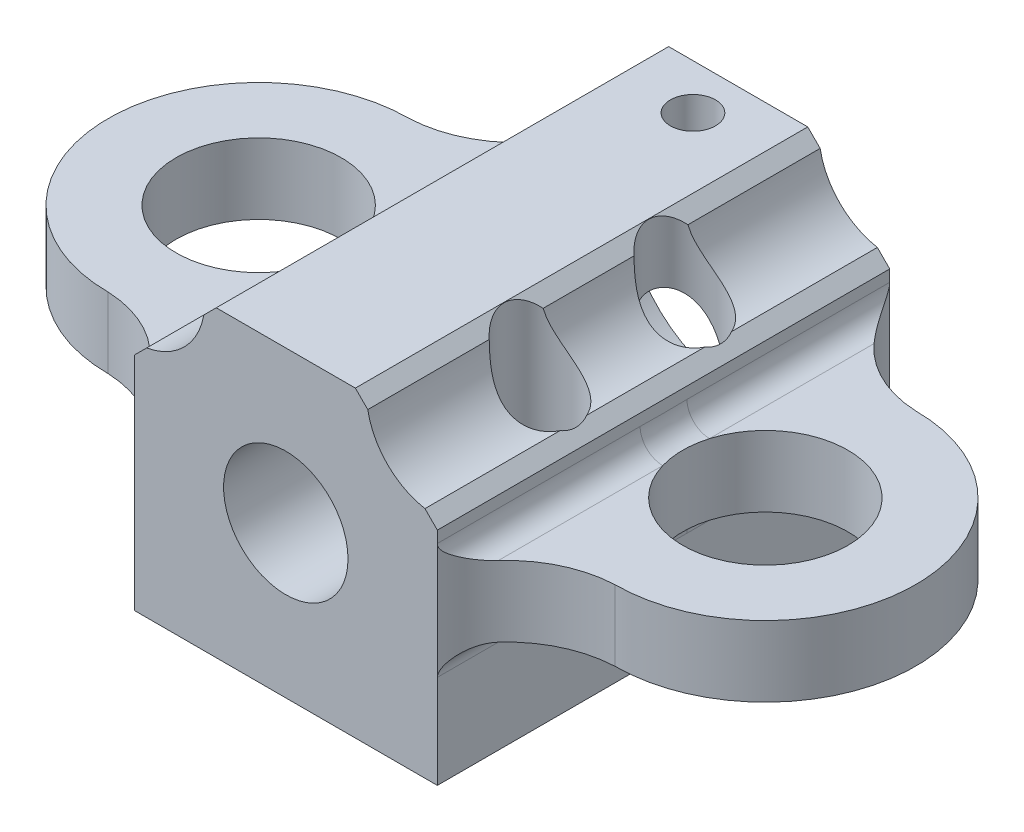
SolidWorks part; units mm, degrees
ref_plane "Front Plane" through (0, 0, 0) normal (0, 0, 1) x (1, 0, 0)
ref_plane "Top Plane" through (0, 0, 0) normal (0, 1, 0) x (1, 0, 0)
ref_plane "Right Plane" through (0, 0, 0) normal (1, 0, 0) x (0, 0, -1)
sketch "Sketch1" plane through (0, 0, 0) normal (0, 0, 1) x (1, 0, 0)
  line L0 (0, 0) -> (0, 69.4209) construction
  line L1 (8.509, 17.018) -> (-8.509, 17.018)
  line L2 (-8.509, 17.018) -> (-8.509, 0)
  line L3 (-8.509, 0) -> (8.509, 0)
  line L4 (8.509, 17.018) -> (8.509, 0)
  point P8 (0, 17.018)
  dimension "D1" = 17.018
  dimension "D2" = 17.018
extrude "Boss-Extrude1" add sketch "Sketch1" along normal blind 25.4
ref_plane "Plane1" through (0, 8.509, 0) normal (0, 1, 0) x (1, 0, 0)
sketch "Sketch2" plane through (0, 0, 0) normal (1, 0, 0) x (0, 0, -1)
  line L0 (-25.4, 8.509) -> (1.0345, 8.509) construction
  line L1 (-25.4, 0) -> (-25.4, 17.018) construction
  line L2 (-12.7, 14.859) -> (0, 14.859)
  line L3 (-12.7, 14.859) -> (-12.7, 12.0015)
  line L4 (-12.7, 12.0015) -> (-25.4, 12.0015)
  line L5 (-25.4, 12.0015) -> (-25.4, 8.509)
  line L6 (-25.4, 17.018) -> (0, 17.018) construction
  line L7 (-25.4, 8.509) -> (-12.1828, 8.509)
  line L9 (0, 0) -> (0, 17.018) construction
  line L10 (-12.1828, 8.509) -> (0, 8.509)
  line L11 (0, 8.509) -> (0, 14.859)
  dimension "D1" = 2.159
  dimension "D2" = 6.985
  dimension "D3" = 12.7
revolve "Cut-Revolve1" cut sketch "Sketch2" angle 360 about L7
sketch "Sketch4" plane through (0, 0, 0) normal (0, -1, 0) x (1, 0, 0)
  line L1 (-6, 17.0663) -> (6, 17.0663) construction
  line L2 (-6, 17.0663) -> (-6, 9.0663) construction
  line L3 (-6, 9.0663) -> (6, 9.0663) construction
  line L4 (6, 17.0663) -> (6, 9.0663) construction
  line L5 (-6, 17.0663) -> (6, 9.0663) construction
  line L6 (-6, 9.0663) -> (6, 17.0663) construction
  line L15 (-8.509, 25.4) -> (8.509, 25.4) construction
  circle A0 centre (-6, 17.0663) radius 1.016
  circle A1 centre (5.938, 17.0663) radius 1.016
  circle A2 centre (5.938, 8.9383) radius 1.016
  circle A3 centre (-6, 8.9383) radius 1.016
  point P0 (0, 13.0663)
  dimension "D3" = 2.032
  dimension "D1" = 12
  dimension "D2" = 8
  dimension "D6" = 8.3337
  dimension "D4" = 2
  dimension "D5" = 2
extrude "Cut-Extrude2" cut sketch "Sketch4" against normal through all
sketch "Sketch5" plane through (0, 8.509, 0) normal (0, 1, 0) x (1, 0, 0)
  line L1 (-14.1338, -12.7) -> (28.118, -12.7) construction
  line L5 (14.224, -12.7) -> (20.4143, -25.9751) construction
  line L8 (8.509, 0) -> (8.509, -25.4)
  line L10 (0, -25.4) -> (0, 11.748) construction
  line L11 (8.509, -25.4) -> (-8.509, -25.4) construction
  line L12 (14.224, 13.3789) -> (14.224, -38.7789) construction
  arc A0 (14.224, -4.2545) -> (14.224, -21.1455) centre (14.224, -12.7) cw
  circle A1 centre (14.224, -12.7) radius 4.6355
  arc A2 (14.224, -21.1455) -> (8.509, -25.4) centre (14.5055, -27.4893) ccw
  arc A3 (14.224, -4.2545) -> (8.509, 0) centre (14.5055, 2.0893) cw
  dimension "D2" = 9.271
  dimension "D4" = 3.81
  dimension "D3" = 6.35
  dimension "D1" = 5.715
  dimension "D5" = 25
extrude "Boss-Extrude2" add sketch "Sketch5" against normal blind 1.9844 and the other way blind 1.9844
mirror "Mirror1" about plane through (0, 0, 0) normal (1, 0, 0) of "Boss-Extrude2"
sketch "Sketch7" plane through (0, 0, 25.4) normal (0, 0, 1) x (1, 0, 0)
  line L0 (0, 19.0675) -> (0, -3.3693) construction
  circle A0 centre (8.509, 17.018) radius 3.9687
  circle A1 centre (-8.509, 17.018) radius 3.9687
  dimension "D1" = 7.9375
extrude "Cut-Extrude3" cut sketch "Sketch7" against normal through all
fillet "Fillet3" radius 1.27 4 edges
chamfer "Chamfer1" distance 0.635 angle 45 4 edges at (8.509, 13.0492, 12.7) (4.5402, 17.018, 12.7) (-4.5402, 17.018, 12.7) (-8.509, 13.0492, 12.7)
sketch "Sketch10" plane through (0, 17.018, 0) normal (0, 1, 0) x (1, 0, 0)
  line L0 (-0.031, -8.9383) -> (-0.031, -21.1529) construction
  line L1 (-6, -8.9383) -> (5.938, -8.9383) construction
  line L2 (-6, -8.9383) -> (-6, -17.0663) construction
  line L3 (-6, -17.0663) -> (5.938, -17.0663) construction
  line L4 (5.938, -8.9383) -> (5.938, -17.0663) construction
  line L5 (5.938, -13.0023) -> (-11.7995, -13.0023) construction
  circle A0 centre (5.938, -8.9383) radius 2.0193
  circle A1 centre (-6, -8.9383) radius 2.0193
  circle A2 centre (5.938, -17.0663) radius 2.0193
  circle A3 centre (-6, -17.0663) radius 2.0193
  dimension "D1" = 4.0386
extrude "Cut-Extrude6" cut sketch "Sketch10" against normal blind 13.97
sketch "Sketch11" plane through (0, 17.018, 0) normal (0, 1, 0) x (1, 0, 0)
  line L0 (5.938, -8.9383) -> (5.938, -28.9543) construction
ref_plane "Plane2" through (5.938, 0, 0) normal (1, 0, 0) x (0, 0, -1)
ref_plane "Plane3" through (0, 8.509, 0) normal (0, 1, 0) x (1, 0, 0)
sketch "Sketch12" plane through (0, 17.018, 0) normal (0, 1, 0) x (1, 0, 0)
  line L0 (3.9053, 0) -> (-3.9053, 0) construction
  circle A0 centre (0, -2.54) radius 1.2662
  dimension "D1" = 2.5324
  dimension "D2" = 2.54
extrude "Cut-Extrude7" cut sketch "Sketch12" against normal blind 2.54
